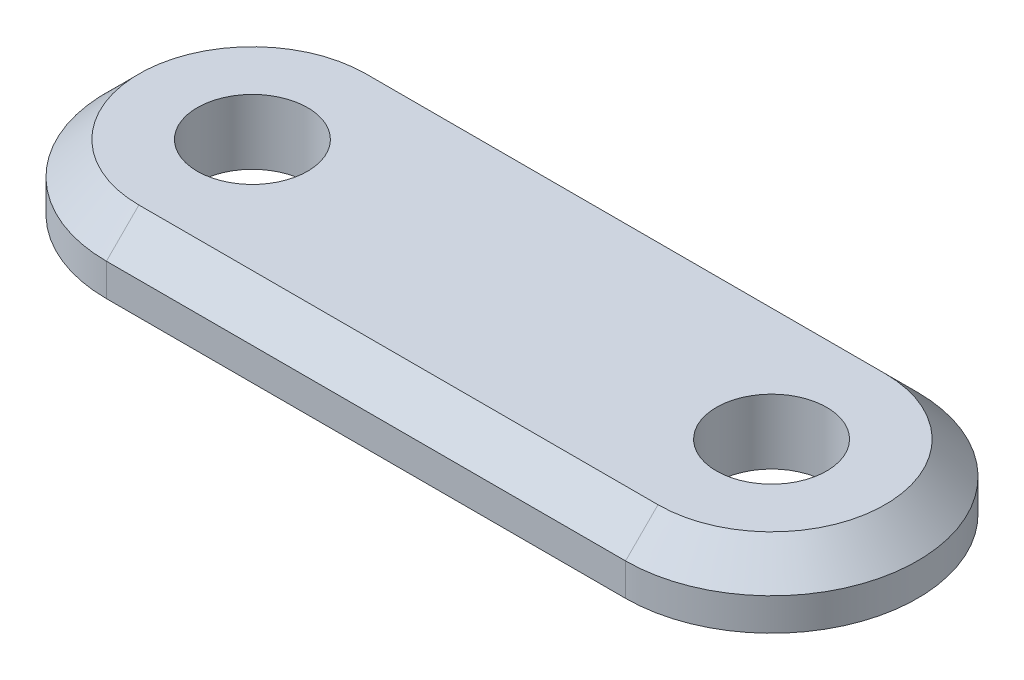
SolidWorks part; units mm, degrees
material "ABS"
ref_plane "Front Plane" through (0, 0, 0) normal (0, 0, 1) x (1, 0, 0)
ref_plane "Top Plane" through (0, 0, 0) normal (0, 1, 0) x (1, 0, 0)
ref_plane "Right Plane" through (0, 0, 0) normal (1, 0, 0) x (0, 0, -1)
sketch "Sketch1" plane through (0, 0, 0) normal (0, 1, 0) x (1, 0, 0)
  line L0 (8, 0) -> (-8, 0) construction
  line L1 (8, -4.5) -> (-8, -4.5)
  line L2 (-2.5, 4.5) -> (-2.5, -4.5) construction
  line L3 (8, 4.5) -> (-8, 4.5)
  line L4 (2.5, 4.5) -> (2.5, -4.5) construction
  line L5 (-2.5, 0) -> (2.5, 0) construction
  line L6 (-4.5, 0) -> (-4.5, -4.5) construction
  circle A0 centre (-8, 0) radius 1.65 construction
  circle A1 centre (8, 0) radius 1.65 construction
  arc A2 (-8, 4.5) -> (-8, -4.5) centre (-8, 0) ccw
  arc A3 (8, -4.5) -> (8, 4.5) centre (8, 0) ccw
  circle A4 centre (-8, 0) radius 3.5 construction
  point P0 (0, 0)
  point P9 (0, 0)
  point P17 (0, 0)
  dimension "D2" = 3.3
  dimension "D5" = 7
  dimension "D4" = 1
  dimension "D6" = 16
  dimension "D1" = 2
  dimension "D3" = 5
extrude "Boss-Extrude1" add sketch "Sketch1" along normal blind 2
sketch "Sketch2" plane through (0, 2, 0) normal (0, 1, 0) x (1, 0, 0)
  line L0 (8, 0) -> (-8, 0)
  arc A1 (-8, 4.5) -> (-8, -4.5) centre (-8, 0) ccw construction
  point P4 (0, 0)
hole_wizard "M3 Clearance Hole1" positions "Sketch4" profile "Sketch3" hole size "M3" standard "ANSI Metric" end condition through all
sketch "Sketch4" plane through (0, 2, 0) normal (0, 1, 0) x (1, 0, 0)
  point P0 (-8, 0)
  point P3 (8, 0)
sketch "Sketch3" plane through (-8, 2, 0) normal (1, 0, 0) x (0, 0, 1)
  line L0 (0, 0) -> (0, 2)
  line L1 (0, 2) -> (1.7, 2)
  line L2 (1.7, 2) -> (1.7, 0)
  line L5 (1.7, 0) -> (0, 0)
  line L11 (0, -6.35) -> (0, 107.95) construction
  dimension "Thru Hole Dia." = 3.4
  dimension "Thru Hole Depth" = 2
chamfer "Chamfer3" distance 1 angle 45 4 edges at (12.5, 2, 0) (0, 2, -4.5) (-12.5, 2, 0) (0, 2, 4.5)
